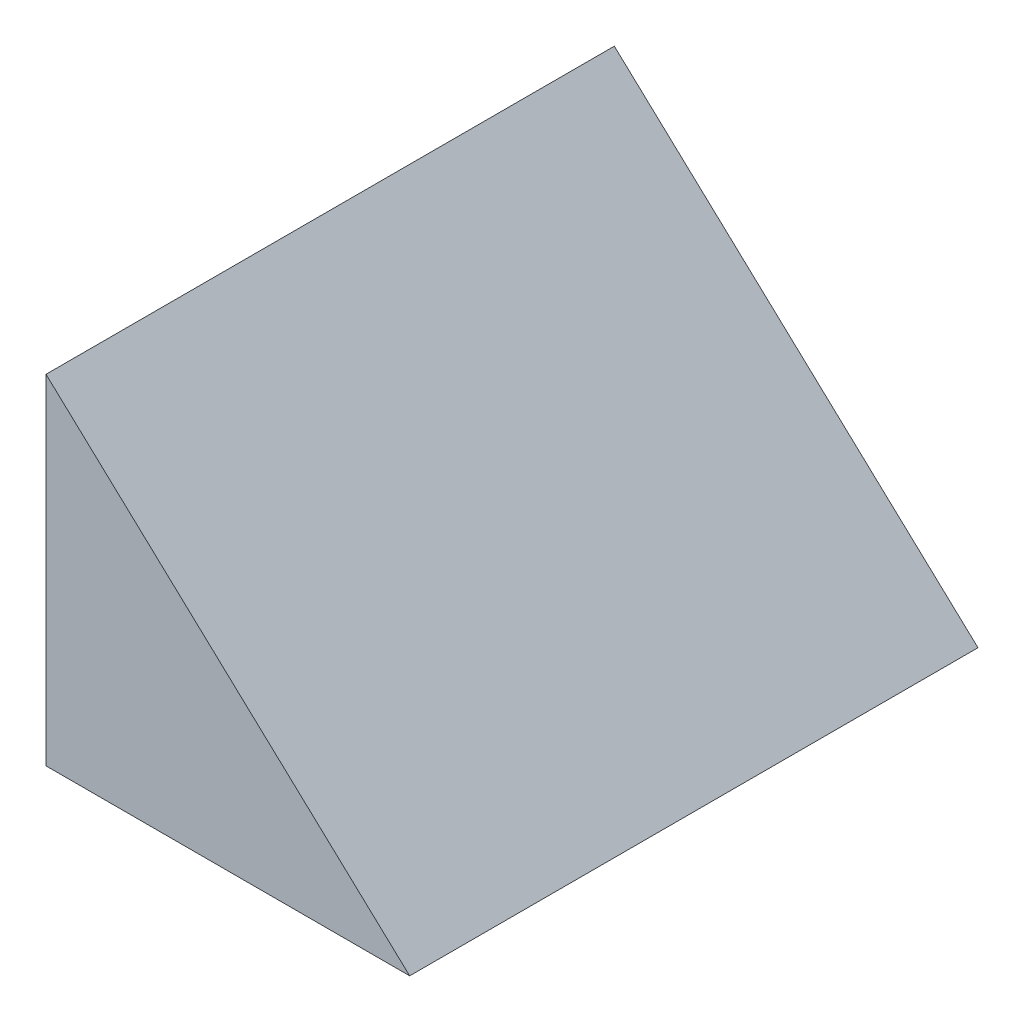
SolidWorks part; units mm, degrees
ref_plane "Front Plane" through (0, 0, 0) normal (0, 0, 1) x (1, 0, 0)
ref_plane "Top Plane" through (0, 0, 0) normal (0, 1, 0) x (1, 0, 0)
ref_plane "Right Plane" through (0, 0, 0) normal (1, 0, 0) x (0, 0, -1)
sketch "Sketch1" plane through (0, 0, 0) normal (0, 0, 1) x (1, 0, 0)
  line L0 (0, 0) -> (25.5974, 0)
  line L1 (25.5974, 0) -> (0, 23.8699)
  line L2 (0, 23.8699) -> (0, 0)
  dimension "D1" = 43
  dimension "D2" = 35
extrude "Boss-Extrude1" add sketch "Sketch1" against normal blind 40
sketch "Sketch3" plane through (0, 0, 0) normal (0, -1, 0) x (1, 0, 0)
  line L0 (0, -40) -> (0, 0) construction
  line L2 (0, 0) -> (25.5974, 0) construction
  circle A0 centre (12.8, -20) radius 1.5
  dimension "D3" = 3
  dimension "D1" = 12.8
  dimension "D2" = 20
extrude "Cut-Extrude1" cut sketch "Sketch3" against normal blind 7
sketch "Sketch6" plane through (0, 0, 0) normal (-1, 0, 0) x (0, 0, 1)
  line L0 (-40, 0) -> (0, 0) construction
  line L1 (-38.5, 0) -> (-1.5, 0)
  line L2 (-38.5, 0) -> (-38.5, 12)
  line L3 (-38.5, 12) -> (-1.5, 12)
  line L4 (-1.5, 0) -> (-1.5, 12)
  line L5 (0, 23.8699) -> (0, 0) construction
  line L6 (-40, 23.8699) -> (-40, 0) construction
  dimension "D1" = 1.5
  dimension "D2" = 1.5
  dimension "D3" = 12
extrude "Cut-Extrude2" cut sketch "Sketch6" against normal blind 10
sketch "Sketch7" plane through (0, 0, 0) normal (-1, 0, 0) x (0, 0, 1)
  line L0 (-40, 23.8699) -> (-40, 0) construction
  line L1 (-38, 19.8699) -> (-2, 19.8699)
  line L2 (-38, 19.8699) -> (-38, 9.8699)
  line L3 (-38, 9.8699) -> (-2, 9.8699)
  line L4 (-2, 19.8699) -> (-2, 9.8699)
  line L5 (0, 23.8699) -> (0, 0) construction
  line L6 (-40, 23.8699) -> (0, 23.8699) construction
  dimension "D1" = 2
  dimension "D2" = 2
  dimension "D3" = 4
  dimension "D4" = 10
extrude "Cut-Extrude3" cut sketch "Sketch7" against normal blind 3.5
sketch "Sketch8" plane through (3.5, 0, 0) normal (-1, 0, 0) x (0, 0, 1)
  line L0 (-38, 12) -> (-2, 12) construction
  line L1 (-36.5, 12) -> (-3.5, 12)
  line L2 (-36.5, 12) -> (-36.5, 16.8699)
  line L3 (-36.5, 16.8699) -> (-3.5, 16.8699)
  line L4 (-3.5, 12) -> (-3.5, 16.8699)
  line L5 (-38, 19.8699) -> (-38, 12) construction
  line L6 (-2, 12) -> (-2, 19.8699) construction
  line L7 (-2, 19.8699) -> (-38, 19.8699) construction
  dimension "D1" = 1.5
  dimension "D2" = 1.5
  dimension "D3" = 3
extrude "Cut-Extrude4" cut sketch "Sketch8" against normal blind 3
sketch "Sketch9" plane through (6.5, 0, 0) normal (-1, 0, 0) x (0, 0, 1)
  line L0 (-36.5, 12) -> (-3.5, 12) construction
  line L1 (-35, 12) -> (-5, 12)
  line L2 (-35, 12) -> (-35, 14.8699)
  line L3 (-35, 14.8699) -> (-5, 14.8699)
  line L4 (-5, 12) -> (-5, 14.8699)
  line L5 (-36.5, 16.8699) -> (-36.5, 12) construction
  line L6 (-3.5, 12) -> (-3.5, 16.8699) construction
  line L7 (-3.5, 16.8699) -> (-36.5, 16.8699) construction
  dimension "D1" = 1.5
  dimension "D2" = 1.5
  dimension "D3" = 2
extrude "Cut-Extrude5" cut sketch "Sketch9" against normal blind 2
